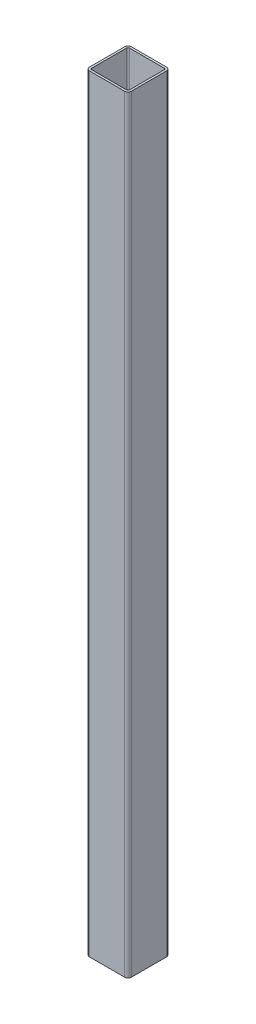
SolidWorks part; units mm, degrees
ref_plane "Спереди" through (0, 0, 0) normal (0, 0, 1) x (1, 0, 0)
ref_plane "Сверху" through (0, 0, 0) normal (0, 1, 0) x (1, 0, 0)
ref_plane "Справа" through (0, 0, 0) normal (1, 0, 0) x (0, 0, -1)
sketch "Эскиз1" plane through (0, 0, 0) normal (0, 1, 0) x (1, 0, 0)
  line L1 (-25, 30) -> (25, 30)
  line L2 (-30, 25) -> (-30, -25)
  line L3 (-25, -30) -> (25, -30)
  line L4 (30, 25) -> (30, -25)
  line L5 (-30, 30) -> (30, -30) construction
  line L6 (-30, -30) -> (30, 30) construction
  arc A0 (-30, -25) -> (-25, -30) centre (-25, -25) ccw
  arc A1 (25, -30) -> (30, -25) centre (25, -25) ccw
  arc A2 (25, 30) -> (30, 25) centre (25, 25) cw
  arc A3 (-25, 30) -> (-30, 25) centre (-25, 25) ccw
  point P0 (0, 0)
  dimension "D1" = 5
  dimension "D2" = 60
  dimension "D3" = 60
extrude "Вытянуть-Тонкостенный1" add sketch "Эскиз1" along normal blind 1100 thin thin type one direction reverse wall 3
